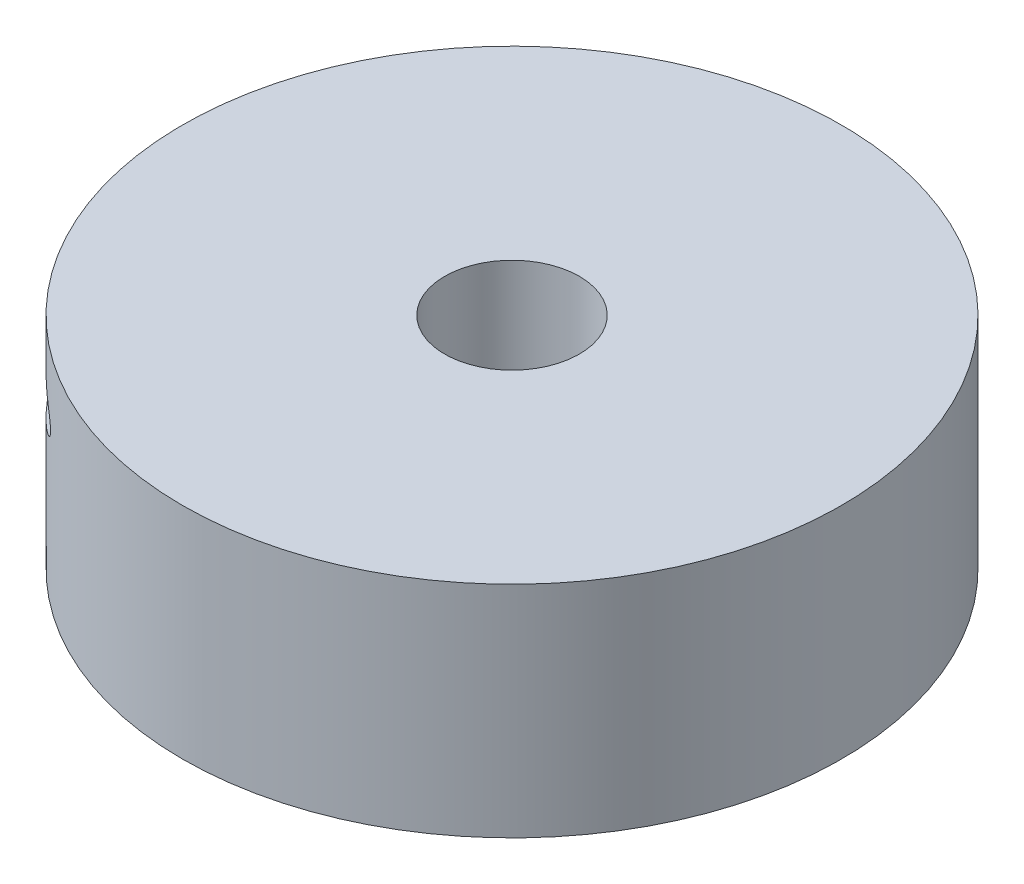
SolidWorks part; units mm, degrees
ref_plane "Front Plane" through (0, 0, 0) normal (0, 0, 1) x (1, 0, 0)
ref_plane "Top Plane" through (0, 0, 0) normal (0, 1, 0) x (1, 0, 0)
ref_plane "Right Plane" through (0, 0, 0) normal (1, 0, 0) x (0, 0, -1)
sketch "Sketch2" plane through (0, 0, 0) normal (0, 1, 0) x (1, 0, 0)
  circle A0 centre (0, 0) radius 28.575
  circle A1 centre (0, 0) radius 5.842
  dimension "D1" = 57.15
  dimension "D2" = 11.684
extrude "Boss-Extrude1" add sketch "Sketch2" along normal blind 19.05
extrude "Cut-Extrude1" cut sketch "Sketch3" against normal through all
sketch "Sketch3" plane through (-19.0365, 184.6238, -47.51) normal (-0.619, -0.0319, -0.7847) x (-0.7851, 0.0006, 0.6193)
  circle A0 centre (44.3535, -173.1756) radius 2.3495
  circle A1 centre (46.6818, 8.1643) radius 2.3495
